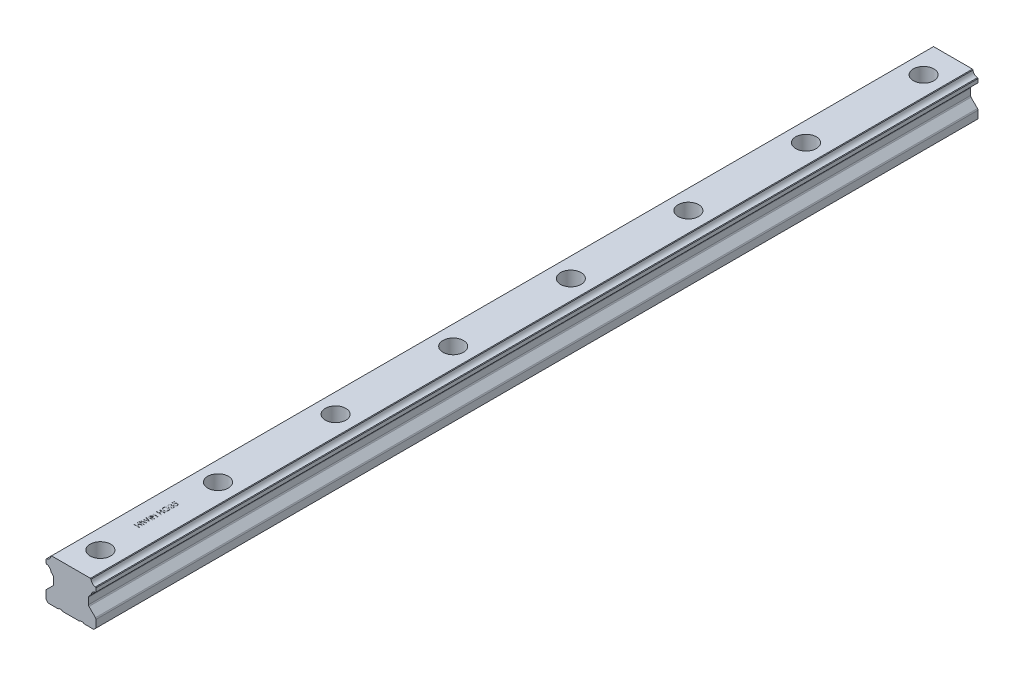
SolidWorks part; units mm, degrees
material "镀铬不锈钢"
ref_plane "前视基准面" through (0, 0, 0) normal (0, 0, 1) x (1, 0, 0)
ref_plane "上视基准面" through (0, 0, 0) normal (0, 1, 0) x (1, 0, 0)
ref_plane "右视基准面" through (0, 0, 0) normal (1, 0, 0) x (0, 0, -1)
sketch "草图1" plane through (0, 0, 0) normal (0, 0, 1) x (1, 0, 0)
  line L28 (-12.2515, 11.8899) -> (-16.6485, 7.4929)
  line L29 (13.2514, 29) -> (-13.2514, 29)
  line L30 (-5.85, 0) -> (5.85, 0)
  line L31 (12.2515, 17.9901) -> (13.6259, 19.3645)
  line L32 (-17, 25.2514) -> (-17, 22.7386)
  line L33 (17, 25.2514) -> (16.6226, 25.6288)
  line L34 (-8.75, 0) -> (-8.25, 0.5)
  line L35 (8.75, 0) -> (15.5, 0)
  line L36 (16.6345, 22.3731) -> (17, 22.7386)
  line L37 (-8.25, 0.5) -> (-6.35, 0.5)
  line L38 (6.35, 0.5) -> (8.25, 0.5)
  line L39 (-15.5, 0) -> (-8.75, 0)
  line L40 (5.85, 0) -> (6.35, 0.5)
  line L41 (13.6268, 28.6246) -> (13.2514, 29)
  line L42 (-17, 1.5) -> (-15.5, 0)
  line L43 (-16.6226, 25.6288) -> (-17, 25.2514)
  line L44 (-11.9, 17.1415) -> (-11.9, 12.7385)
  line L45 (-6.35, 0.5) -> (-5.85, 0)
  line L46 (17, 22.7386) -> (17, 25.2514)
  line L47 (17, 1.5) -> (17, 6.6443)
  line L48 (16.6485, 7.4929) -> (12.2515, 11.8899)
  line L49 (-13.2514, 29) -> (-13.6268, 28.6246)
  line L50 (-17, 22.7386) -> (-16.6345, 22.3731)
  line L51 (-13.6259, 19.3645) -> (-12.2515, 17.9901)
  line L52 (8.25, 0.5) -> (8.75, 0)
  line L53 (15.5, 0) -> (17, 1.5)
  line L54 (11.9, 12.7385) -> (11.9, 17.1415)
  line L55 (-17, 6.6443) -> (-17, 1.5)
  arc A10 (-11.9, 17.1415) -> (-12.2515, 17.9901) centre (-13.1, 17.1415) ccw
  arc A11 (11.9, 12.7385) -> (12.2515, 11.8899) centre (13.1, 12.7385) ccw
  arc A12 (16.6345, 22.3731) -> (13.6259, 19.3645) centre (16.8676, 19.1314) ccw
  arc A13 (17, 6.6443) -> (16.6485, 7.4929) centre (15.8, 6.6443) ccw
  arc A14 (-16.6226, 25.6288) -> (-13.6268, 28.6246) centre (-16.8676, 28.8696) ccw
  arc A15 (-12.2515, 11.8899) -> (-11.9, 12.7385) centre (-13.1, 12.7385) ccw
  arc A16 (-16.6485, 7.4929) -> (-17, 6.6443) centre (-15.8, 6.6443) ccw
  arc A17 (-13.6259, 19.3645) -> (-16.6345, 22.3731) centre (-16.8676, 19.1314) ccw
  arc A18 (13.6268, 28.6246) -> (16.6226, 25.6288) centre (16.8676, 28.8696) ccw
  arc A19 (12.2515, 17.9901) -> (11.9, 17.1415) centre (13.1, 17.1415) ccw
extrude "凸台-拉伸1" add sketch "草图1" against normal blind 600
hole_wizard "M8 六角凹头螺钉的柱形沉头孔1" positions "草图3" profile "草图2" counterbore size "M8" standard "ISO" end condition through all
sketch "草图3" plane through (-5.4771, 29, -56.1162) normal (0, 1, 0) x (-1, 0, 0)
  point P0 (-5.4771, 36.1162)
  dimension "D1" = 20
sketch "草图2" plane through (0, 29, -20) normal (1, 0, 0) x (0, 0, 1)
  line L0 (0, 0) -> (0, 29)
  line L1 (0, 29) -> (4.5, 29)
  line L3 (4.5, 29) -> (4.5, 12)
  line L4 (4.5, 12) -> (7, 12)
  line L5 (7, 12) -> (7, 0)
  line L7 (7, 0) -> (0, 0)
  line L11 (0, -6.35) -> (0, 107.95) construction
  dimension "通孔孔直径" = 9
  dimension "通孔孔深度" = 29
  dimension "柱形沉头孔直径" = 14
  dimension "柱形沉头孔深度" = 12
pattern_linear "阵列(线性)1" count 8 spacing 80 along (0, 0, -1) of "M8 六角凹头螺钉的柱形沉头孔1"
sketch "草图6" plane through (0, 29, 0) normal (0, 1, 0) x (1, 0, 0)
  line L0 (0, 20) -> (0, 100) construction
  text T0 "HIWIN HG35"
extrude "切除-拉伸1" cut sketch "草图6" against normal blind 0.1
equation "\"D1@凸台-拉伸1\" = 2 * \"D1@草图3\" + \"D3@阵列(线性)1\" *  ( \"D1@阵列(线性)1\"  - 1) "
